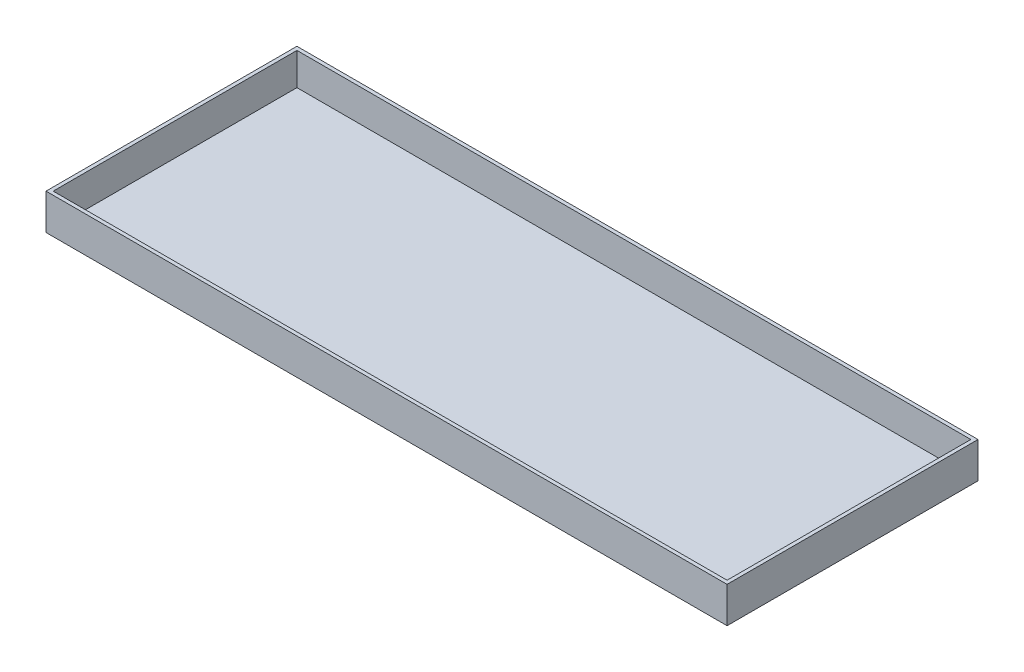
SolidWorks part; units mm, degrees
ref_plane "Ebene vorne" through (0, 0, 0) normal (0, 0, 1) x (1, 0, 0)
ref_plane "Ebene oben" through (0, 0, 0) normal (0, 1, 0) x (1, 0, 0)
ref_plane "Ebene rechts" through (0, 0, 0) normal (1, 0, 0) x (0, 0, -1)
sketch "Skizze1" plane through (0, 0, 0) normal (1, 0, 0) x (0, 0, -1)
  line L1 (0, 0) -> (350, 0)
  line L2 (0, 0) -> (0, 50)
  line L3 (0, 50) -> (350, 50)
  line L4 (350, 0) -> (350, 50)
  dimension "D1" = 50
  dimension "D2" = 350
extrude "Aufsatz-Linear austragen1" add sketch "Skizze1" along normal blind 950
sketch "Skizze2" plane through (0, 50, 0) normal (0, 1, 0) x (1, 0, 0)
  line L0 (0, 350) -> (0, 0) construction
  line L1 (5, 345) -> (945, 345)
  line L2 (5, 345) -> (5, 5)
  line L3 (5, 5) -> (945, 5)
  line L4 (945, 345) -> (945, 5)
  line L5 (950, 350) -> (950, 0) construction
  line L6 (950, 350) -> (0, 350) construction
  line L7 (950, 0) -> (0, 0) construction
  dimension "D1" = 5
  dimension "D2" = 5
  dimension "D3" = 5
  dimension "D4" = 5
extrude "Schnitt-Linear austragen1" cut sketch "Skizze2" against normal blind 45
